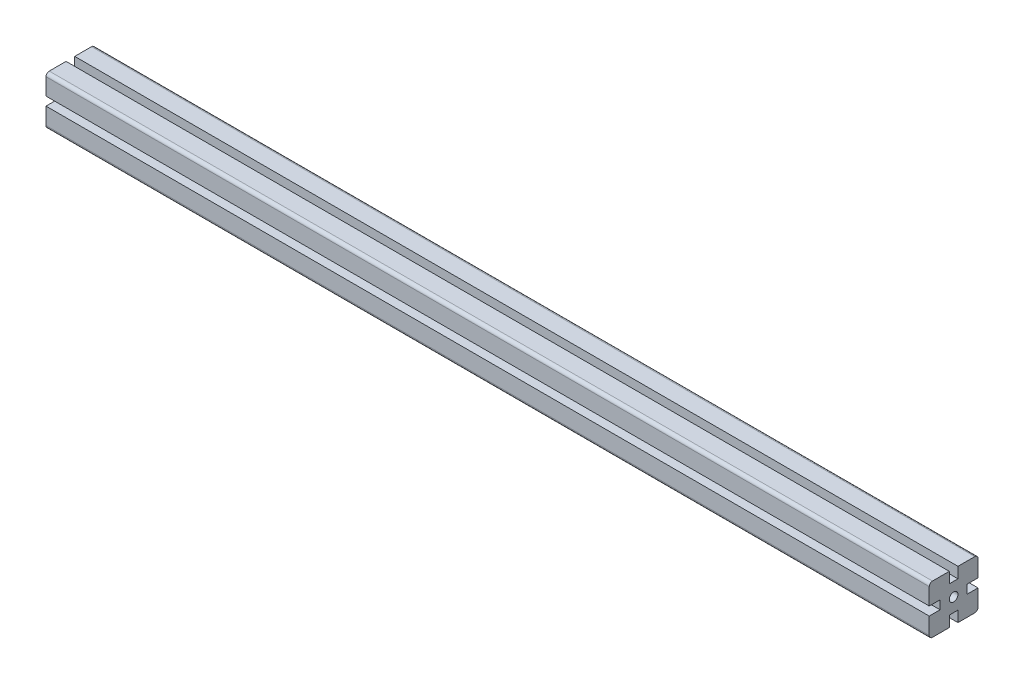
SolidWorks part; units mm, degrees
ref_plane "Plan de face" through (0, 0, 0) normal (0, 0, 1) x (1, 0, 0)
ref_plane "Plan de dessus" through (0, 0, 0) normal (0, 1, 0) x (1, 0, 0)
ref_plane "Plan de droite" through (0, 0, 0) normal (1, 0, 0) x (0, 0, -1)
ref_plane "Plan1" through (1000, 0, 0) normal (1, 0, 0) x (0, 0, -1)
sketch "Esquisse1" plane through (1000, 0, 0) normal (1, 0, 0) x (0, 0, -1)
  line L0 (22.5, -4) -> (12.5, -4)
  line L1 (12.5, -4) -> (12.5, 4)
  line L2 (12.5, 4) -> (22.5, 4)
  line L3 (22.5, 4) -> (22.5, 22.5)
  line L4 (22.5, 22.5) -> (4, 22.5)
  line L5 (4, 22.5) -> (4, 12.5)
  line L6 (4, 12.5) -> (-4, 12.5)
  line L7 (-4, 12.5) -> (-4, 22.5)
  line L8 (-4, 22.5) -> (-22.5, 22.5)
  line L9 (-22.5, 22.5) -> (-22.5, 4)
  line L10 (-22.5, 4) -> (-12.5, 4)
  line L11 (-12.5, 4) -> (-12.5, -4)
  line L12 (-12.5, -4) -> (-22.5, -4)
  line L13 (-22.5, -4) -> (-22.5, -22.5)
  line L14 (-22.5, -22.5) -> (-4, -22.5)
  line L15 (-4, -22.5) -> (-4, -12.5)
  line L16 (-4, -12.5) -> (4, -12.5)
  line L17 (4, -12.5) -> (4, -22.5)
  line L18 (4, -22.5) -> (22.5, -22.5)
  line L19 (22.5, -22.5) -> (22.5, -4)
  line L20 (0, 0) -> (22.5, 0) construction
  line L21 (0, 0) -> (0, 22.5) construction
  circle A0 centre (0, 0) radius 4
  dimension "D1" = 4
  dimension "D2" = 45
  dimension "D3" = 45
  dimension "D4" = 4
  dimension "D5" = 10
  dimension "D6" = 10
  dimension "D7" = 22.5
extrude "Boss.-Extru.1" add sketch "Esquisse1" against normal blind 815
fillet "Congé1" radius 3 4 edges at (592.5, -22.5, -22.5) (592.5, 22.5, -22.5) (592.5, -22.5, 22.5) (592.5, 22.5, 22.5)
ref_axis "Axis1" through (7.3291, 0, 0) along (1, 0, 0)
